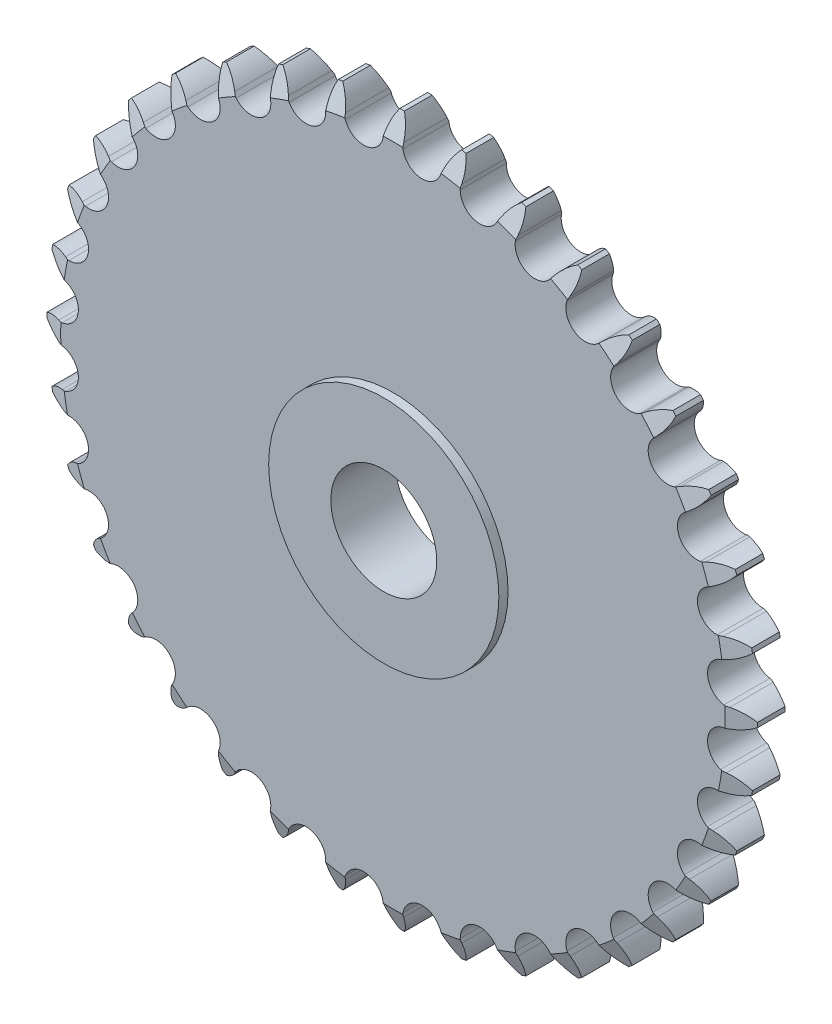
SolidWorks part; units mm, degrees
ref_plane "Front Plane" through (0, 0, 0) normal (0, 0, 1) x (1, 0, 0)
ref_plane "Top Plane" through (0, 0, 0) normal (0, 1, 0) x (1, 0, 0)
ref_plane "Right Plane" through (0, 0, 0) normal (1, 0, 0) x (0, 0, -1)
sketch "Sketch1" plane through (0, 0, 0) normal (0, 0, 1) x (1, 0, 0)
  line L0 (0, 0) -> (0, 72.8581) construction
  line L1 (-2.1568, 71.8581) -> (2.1568, 71.8581) construction
  line L2 (-2.1568, 71.8581) -> (-2.0429, 72.8581) construction
  line L3 (2.1568, 71.8581) -> (2.0429, 72.8581) construction
  line L4 (-2.0429, 72.8581) -> (2.0429, 72.8581) construction
  line L7 (-0.5, 77.163) -> (0.5, 77.163) construction
  circle A0 centre (0, 0) radius 72.8581 construction
  circle A1 centre (6.35, 72.5808) radius 4.255 construction
  circle A2 centre (-6.35, 72.5808) radius 4.255 construction
  circle A3 centre (0, 0) radius 68.6031 construction
  arc A4 (-2.0429, 72.8581) -> (-0.5, 77.163) centre (7.8928, 71.726) cw construction
  arc A5 (2.0429, 72.8581) -> (0.5, 77.163) centre (-7.8928, 71.726) ccw construction
  dimension "D1" = 13
  dimension "SprocketPitchDiameter" = 145.7162
  dimension "RollerDia" = 8.51
  dimension "D4" = 10
  dimension "ChainPitch" = 12.7
  dimension "D2" = 1
  dimension "D3" = 1
  dimension "D5" = 1
sketch "Sketch2" plane through (0, 0, 0) normal (0, 0, 1) x (1, 0, 0)
  circle A0 centre (0, 0) radius 68.6031 construction
  circle A1 centre (0, 0) radius 68.6031
extrude "Boss-Extrude1" add sketch "Sketch2" along normal mid plane 10
sketch "Sketch4" plane through (0, 0, 0) normal (0, 0, 1) x (1, 0, 0)
  line L0 (-0.5, 77.163) -> (0.5, 77.163) construction
  line L1 (-2.1568, 71.8581) -> (-2.0429, 72.8581) construction
  line L2 (2.1568, 71.8581) -> (2.0429, 72.8581) construction
  line L3 (-0.5, 77.163) -> (0.5, 77.163)
  line L4 (-2.1568, 71.8581) -> (-2.0429, 72.8581)
  line L5 (2.1568, 71.8581) -> (2.0429, 72.8581)
  circle A0 centre (0, 0) radius 68.6031 construction
  circle A1 centre (6.35, 72.5808) radius 4.255 construction
  circle A2 centre (-6.35, 72.5808) radius 4.255 construction
  arc A3 (2.0429, 72.8581) -> (0.5, 77.163) centre (-7.8928, 71.726) ccw construction
  arc A4 (-0.5, 77.163) -> (-2.0429, 72.8581) centre (7.8928, 71.726) ccw construction
  arc A5 (5.9792, 68.342) -> (-5.9792, 68.342) centre (0, 0) ccw
  arc A6 (2.1568, 71.8581) -> (5.9792, 68.342) centre (6.35, 72.5808) ccw
  arc A7 (-5.9792, 68.342) -> (-2.1568, 71.8581) centre (-6.35, 72.5808) ccw
  arc A8 (2.0429, 72.8581) -> (0.5, 77.163) centre (-7.8928, 71.726) ccw
  arc A9 (-0.5, 77.163) -> (-2.0429, 72.8581) centre (7.8928, 71.726) ccw
extrude "Boss-Extrude2" add sketch "Sketch4" along normal up to surface and the other way up to surface up to face at (68.6031, 0, 5) other way up to face at (68.6031, 0, -5)
pattern_circular "CirPattern1" count 36 over 360 about axis through (0, 0, 5) along (0, 0, -1) of "Boss-Extrude2"
sketch "Sketch5" plane through (0, 0, 0) normal (1, 0, 0) x (0, 0, -1)
  line L0 (0, 0) -> (-6, 0) construction
  line L1 (0, 77.163) -> (0, 72.8581) construction
  line L2 (-6, 84.663) -> (6, 84.663)
  line L3 (-6, 84.663) -> (-6, 69.663)
  line L4 (-6, 69.663) -> (6, 69.663) construction
  line L5 (6, 84.663) -> (6, 69.663)
  line L6 (-6, 84.663) -> (6, 69.663) construction
  line L7 (-6, 69.663) -> (6, 84.663) construction
  line L8 (-6, 69.663) -> (0, 84.663)
  line L9 (6, 69.663) -> (0, 84.663)
  line L10 (0, 77.163) -> (0, 72.8581) construction
  point P1 (0, 77.163)
  dimension "D1" = 15
  dimension "D2" = 1
revolve "Cut-Revolve7" cut sketch "Sketch5" angle 360 about L0 region at (0, 79.663, -4) region at (0, 79.663, 4)
sketch "Sketch6" plane through (0, 0, 0) normal (0, 0, 1) x (1, 0, 0)
  circle A0 centre (0, 0) radius 25
  dimension "D1" = 50
extrude "Boss-Extrude3" add sketch "Sketch6" along normal mid plane 14
sketch "Sketch7" plane through (0, 0, 0) normal (0, 0, 1) x (1, 0, 0)
  circle A0 centre (0, 0) radius 11.5
  dimension "D1" = 23
extrude "Cut-Extrude1" cut sketch "Sketch7" against normal through all both and the other way through all
equation "\"ChainPitch\"=12.7"
equation "\"ChainPitch@Sketch1\"=\"ChainPitch\""
equation "\"SprocketPitchDiameter@Sketch1\" = \"ChainPitch\" / sin ( 180 / \"NumberOfTeeth\" )"
equation "\"NumberOfTeeth\"= 36"
equation "\"D1@CirPattern1\"=\"NumberOfTeeth\""
